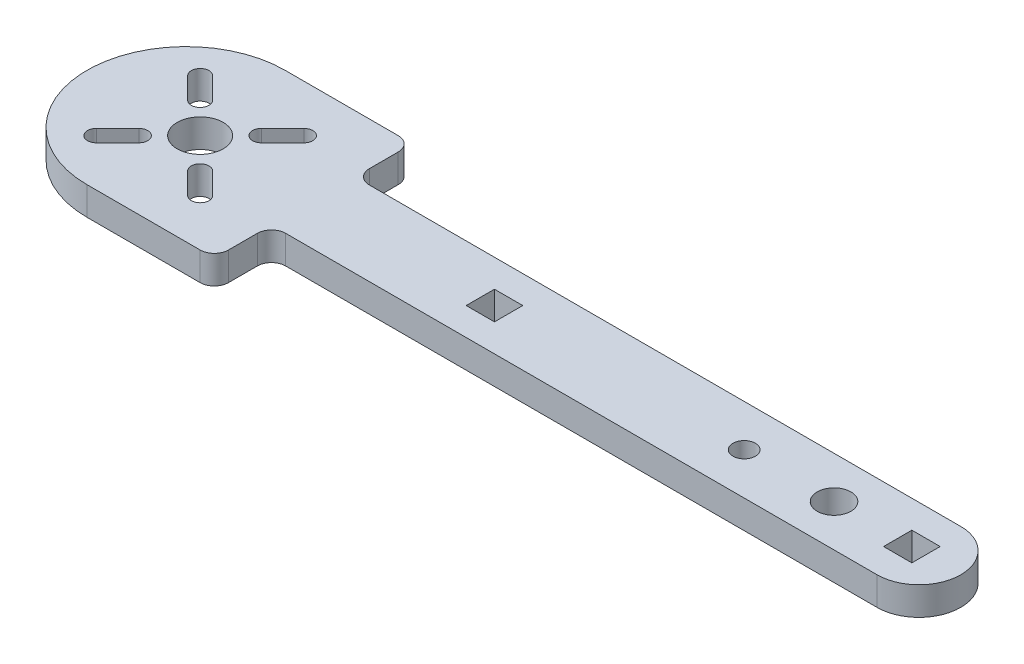
SolidWorks part; units mm, degrees
material "Thornel VCB-20 Carbon Cloth"
ref_plane "Front Plane" through (0, 0, 0) normal (0, 0, 1) x (1, 0, 0)
ref_plane "Top Plane" through (0, 0, 0) normal (0, 1, 0) x (1, 0, 0)
ref_plane "Right Plane" through (0, 0, 0) normal (1, 0, 0) x (0, 0, -1)
sketch "Sketch1" plane through (0, 0, 0) normal (0, 1, 0) x (1, 0, 0)
  line L0 (-58.0134, 7.2134) -> (-43.5866, -7.2134) construction
  line L1 (-50.8, 14) -> (-36.8, 14)
  line L2 (-50.8, 14) -> (-50.8, -14) construction
  line L3 (-50.8, -14) -> (-36.8, -14)
  line L7 (-58.4887, -7.6887) -> (-43.1113, 7.6887) construction
  line L8 (-58.1362, 7.3362) -> (-55.131, 4.331) construction
  line L9 (-57.2523, 8.2201) -> (-54.2471, 5.2149)
  line L10 (-59.0201, 6.4523) -> (-56.0149, 3.4471)
  line L11 (-43.4638, 7.3362) -> (-46.469, 4.331) construction
  line L12 (-42.5799, 6.4523) -> (-45.5851, 3.4471)
  line L13 (-44.3477, 8.2201) -> (-47.3529, 5.2149)
  line L14 (-43.4638, -7.3362) -> (-46.469, -4.331) construction
  line L15 (-44.3477, -8.2201) -> (-47.3529, -5.2149)
  line L16 (-42.5799, -6.4523) -> (-45.5851, -3.4471)
  line L17 (-58.1362, -7.3362) -> (-55.131, -4.331) construction
  line L18 (-59.0201, -6.4523) -> (-56.0149, -3.4471)
  line L19 (-57.2523, -8.2201) -> (-54.2471, -5.2149)
  line L21 (-34.8, 7.9146) -> (-34.8, 12)
  line L24 (-34.8, -12) -> (-34.8, -7.9146)
  line L32 (-32.8, 5.9146) -> (50.8, 5.9146)
  line L33 (-32.8, -5.9146) -> (50.8, -5.9146)
  line L34 (-50.8, 0) -> (50.8, 0) construction
  line L35 (-50.8, 14) -> (-52.8, 14)
  line L36 (-50.8, -14) -> (-52.8, -14)
  line L38 (47.8, -2) -> (51.8, -2)
  line L39 (47.8, -2) -> (47.8, 2)
  line L40 (47.8, 2) -> (51.8, 2)
  line L41 (51.8, -2) -> (51.8, 2)
  line L42 (47.8, -2) -> (51.8, 2) construction
  line L43 (47.8, 2) -> (51.8, -2) construction
  line L44 (-11.2, -2) -> (-7.2, -2)
  line L45 (-11.2, -2) -> (-11.2, 2)
  line L46 (-11.2, 2) -> (-7.2, 2)
  line L47 (-7.2, -2) -> (-7.2, 2)
  line L48 (-11.2, -2) -> (-7.2, 2) construction
  line L49 (-11.2, 2) -> (-7.2, -2) construction
  circle A2 centre (-50.8, 0) radius 3.25
  arc A3 (-57.2523, 8.2201) -> (-59.0201, 6.4523) centre (-58.1362, 7.3362) ccw
  arc A4 (-56.0149, 3.4471) -> (-54.2471, 5.2149) centre (-55.131, 4.331) ccw
  arc A5 (-42.5799, 6.4523) -> (-44.3477, 8.2201) centre (-43.4638, 7.3362) ccw
  arc A6 (-47.3529, 5.2149) -> (-45.5851, 3.4471) centre (-46.469, 4.331) ccw
  arc A7 (-44.3477, -8.2201) -> (-42.5799, -6.4523) centre (-43.4638, -7.3362) ccw
  arc A8 (-45.5851, -3.4471) -> (-47.3529, -5.2149) centre (-46.469, -4.331) ccw
  arc A9 (-59.0201, -6.4523) -> (-57.2523, -8.2201) centre (-58.1362, -7.3362) ccw
  arc A10 (-54.2471, -5.2149) -> (-56.0149, -3.4471) centre (-55.131, -4.331) ccw
  arc A12 (-34.8, -7.9146) -> (-32.8, -5.9146) centre (-32.8, -7.9146) cw
  arc A13 (-32.8, 5.9146) -> (-34.8, 7.9146) centre (-32.8, 7.9146) cw
  arc A14 (-36.8, -14) -> (-34.8, -12) centre (-36.8, -12) ccw
  arc A15 (-34.8, 12) -> (-36.8, 14) centre (-36.8, 12) ccw
  arc A16 (50.8, 5.9146) -> (50.8, -5.9146) centre (50.8, 0) cw
  arc A17 (-52.8, -14) -> (-52.8, 14) centre (-52.8, 0) cw
  circle A18 centre (38.8, 0) radius 2.3812
  circle A19 centre (26.1, 0) radius 1.5875
  circle A20 centre (26.1, 0) radius 2.3749
  point P0 (0, 0)
  point P12 (-50.8, 0)
  point P14 (-50.8, 0)
  point P17 (-56.6336, 5.8336)
  point P27 (-44.9664, 5.8336)
  point P34 (-44.9664, -5.8336)
  point P41 (-56.6336, -5.8336)
  point P46 (-50.8, 0)
  point P53 (-34.8, -7)
  point P56 (-34.8, 7)
  point P59 (-34.8, -14)
  point P62 (-34.8, 14)
  point P64 (49.8, 0)
  point P70 (-9.2, 0)
  dimension "D3" = 6.5
  dimension "D6" = 8.25
  dimension "D10" = 4.7625
  dimension "D17" = 2
  dimension "D18" = 2
  dimension "D16" = 5.9146
  dimension "D2" = 14
  dimension "D21" = 4
  dimension "D22" = 4
  dimension "D27" = 3.175
  dimension "D29" = 4.7498
  dimension "D4" = 45
  dimension "D5" = 45
  dimension "D7" = 4.25
  dimension "D8" = 2.5
  dimension "D11" = 16
  dimension "D12" = 16
  dimension "D13" = 7
  dimension "D14" = 7
  dimension "D15" = 101.6
  dimension "D19" = 50.8
  dimension "D20" = 2
  dimension "D23" = 1
  dimension "D24" = 12
  dimension "D25" = 4
  dimension "D26" = 60
  dimension "D28" = 12.7
  dimension "D9" = 4
extrude "Boss-Extrude1" add sketch "Sketch1" along normal blind 4 contours A17 L36 L3 A14 L24 A12 L33 A16 L32 A13 L21 A15 L1 L35 A20 A18 A10 L19 A9 L18 A8 L16 A7 L15 A6 L13 A5 L12 A4 L10 A3 L9 A2 L47 L44 L45 L46 L41 L38 L39 L40 | A20 A19 region at (-15.1991, 0, 0) region at (23.7923, 0, 0)
extrude "Cut-Extrude1" cut sketch "Sketch1<3>" along normal blind 0.8128 contours A20
sketch "Sketch1<3>" plane through (0, 0, 0) normal (0, 1, 0) x (1, 0, 0) same geometry as "Sketch1"
